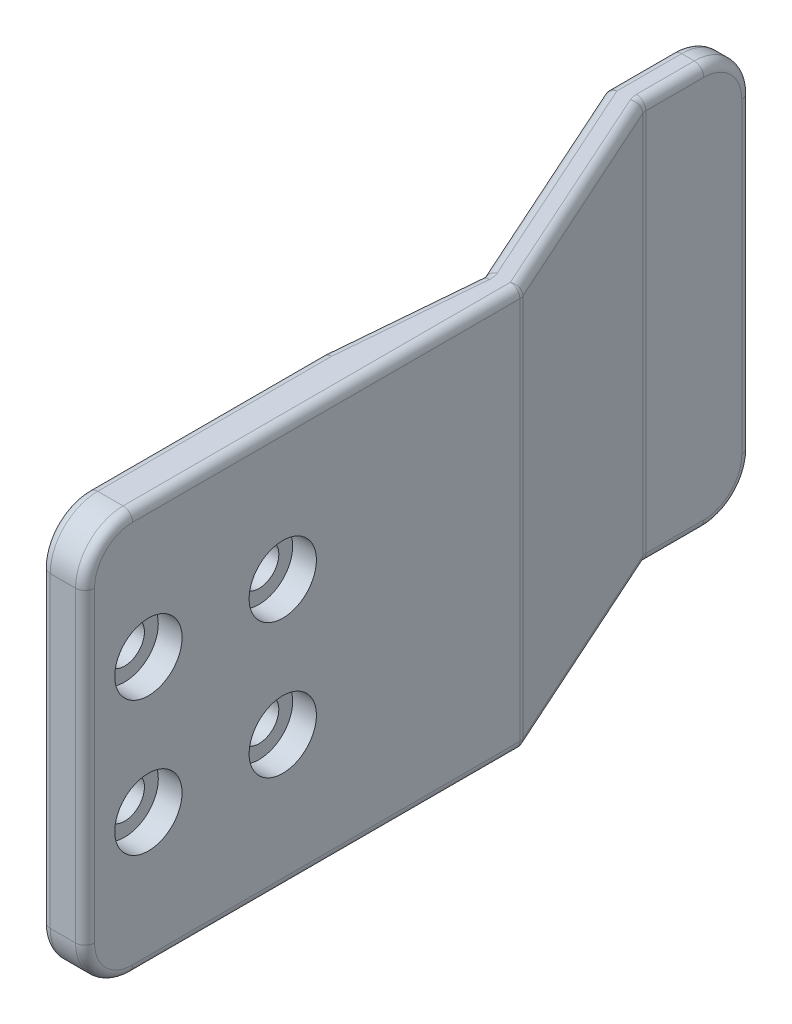
SolidWorks part; units mm, degrees
ref_plane "Front Plane" through (0, 0, 0) normal (0, 0, 1) x (1, 0, 0)
ref_plane "Top Plane" through (0, 0, 0) normal (0, 1, 0) x (1, 0, 0)
ref_plane "Right Plane" through (0, 0, 0) normal (1, 0, 0) x (0, 0, -1)
sketch "Sketch1" plane through (0, 0, 0) normal (0, 0, 1) x (1, 0, 0)
  line L0 (0, 0) -> (0, 24.7759) construction
  line L1 (0, 0) -> (34.3441, 0) construction
  line L3 (7, 12.7) -> (9, 12.7)
  line L4 (7, 12.7) -> (7, -12.7)
  line L5 (7, -12.7) -> (9, -12.7)
  line L6 (9, 12.7) -> (9, -12.7)
  line L7 (7, 12.7) -> (9, -12.7) construction
  line L8 (7, -12.7) -> (9, 12.7) construction
  point P3 (8, 0)
  dimension "D1" = 7
  dimension "D2" = 2
  dimension "D3" = 25.4
sketch "Sketch2" plane through (0, 0, 0) normal (0, 1, 0) x (1, 0, 0)
  line L0 (8, 0) -> (8, 27.37)
  line L1 (8, 27.37) -> (1.7, 41.37)
  line L2 (1.7, 41.37) -> (1.7, 48.37)
  line L3 (0, 0) -> (0, 51.9607) construction
  dimension "D1" = 1.7
  dimension "D2" = 7
  dimension "D4" = 21
  dimension "D3" = 48.37
sweep "Sweep1" add profiles "Sketch1" path "Sketch2"
sketch "Sketch8" plane through (9, 0, 0) normal (1, 0, 0) x (0, 0, -1)
  line L1 (12.4853, -4.2426) -> (4, -4.2426) construction
  line L2 (12.4853, -4.2426) -> (12.4853, 4.2426) construction
  line L3 (12.4853, 4.2426) -> (4, 4.2426) construction
  line L4 (4, -4.2426) -> (4, 4.2426) construction
  line L5 (12.4853, -4.2426) -> (4, 4.2426) construction
  line L6 (12.4853, 4.2426) -> (4, -4.2426) construction
  line L7 (0, -12.7) -> (0, 12.7) construction
  circle A0 centre (4, 4.2426) radius 1.25
  circle A1 centre (12.4853, 4.2426) radius 1.25
  circle A2 centre (4, -4.2426) radius 1.25
  circle A3 centre (12.4853, -4.2426) radius 1.25
  point P0 (8.2426, 0)
  dimension "D3" = 2.5
  dimension "D2" = 6
  dimension "D1" = 4
extrude "Bracket Thru Holes" cut sketch "Sketch8" against normal through all
sketch "Sketch9" plane through (7, 0, 0) normal (-1, 0, 0) x (0, 0, 1)
  line L0 (-12.4853, 4.2426) -> (-4, 4.2426) construction
  line L1 (-8.2426, 4.2426) -> (-8.2426, 12.7) construction
  line L2 (-27.1554, 12.7) -> (0, 12.7) construction
  line L3 (-27.1554, -12.7) -> (0, -12.7) construction
  line L4 (0, 12.7) -> (-16.4853, 12.7)
  line L5 (0, 12.7) -> (0, -12.7)
  line L6 (0, -12.7) -> (-16.4853, -12.7)
  line L7 (-16.4853, 12.7) -> (-16.4853, -12.7)
  circle A0 centre (-4, -4.2426) radius 1.25 construction
  circle A1 centre (-12.4853, -4.2426) radius 1.25 construction
  circle A2 centre (-4, 4.2426) radius 1.25 construction
  circle A3 centre (-12.4853, 4.2426) radius 1.25 construction
  circle A4 centre (-4, -4.2426) radius 1.25
  circle A5 centre (-12.4853, -4.2426) radius 1.25
  circle A6 centre (-4, 4.2426) radius 1.25
  circle A7 centre (-12.4853, 4.2426) radius 1.25
  point P15 (-8.2426, 12.7)
extrude "Bracket Thicken" add sketch "Sketch9" along normal blind 0.8
sketch "Sketch10" plane through (0, 12.7, 0) normal (0, 1, 0) x (1, 0, 0)
  line L0 (6.2, 16.4853) -> (6.2, 17.7853)
  line L1 (7, 27.1554) -> (7, 16.4853)
  line L2 (7, 16.4853) -> (6.2, 16.4853)
  line L3 (6.2, 17.7853) -> (7, 27.1554)
  dimension "D1" = 1.3
extrude "Bracket Thicken Chamfer" add sketch "Sketch10" against normal through all
sketch "Sketch11" plane through (9, 0, 0) normal (1, 0, 0) x (0, 0, -1)
  circle A0 centre (4, 4.2426) radius 2.125
  circle A1 centre (12.4853, 4.2426) radius 2.125
  circle A2 centre (4, -4.2426) radius 2.125
  circle A3 centre (12.4853, -4.2426) radius 2.125
  dimension "D1" = 4.25
extrude "Bracket Bore Holes" cut sketch "Sketch11" against normal blind 1.5
fillet "Fillet1" radius 3 4 edges at (7.6, 12.7, 0) (7.6, -12.7, 0) (1.7, -12.7, -48.37) (1.7, 12.7, -48.37)
fillet "Fillet2" radius 0.6 31 edges at (0.7, -11.8213, -47.4913) (0.7, 0, -48.37) (0.7, 11.8213, -47.4913) (2.7, -11.8213, -47.4913) (2.7, 0, -48.37) (2.7, 11.8213, -47.4913) (9, -11.8213, -0.8787) (9, 0, 0) (9, 11.8213, -0.8787) (6.2, -11.8213, -0.8787) (6.2, 0, 0) (6.2, 11.8213, -0.8787) (5.85, -12.7, -34.5846) (2.7, -12.7, -43.4773) (0.7, -12.7, -43.2627) (3.85, -12.7, -34.1554) (6.2, -12.7, -10.3926) (9, -12.7, -15.2923) (3.85, 12.7, -34.1554) (0.7, 12.7, -43.2627) (2.7, 12.7, -43.4773) (5.85, 12.7, -34.5846) (9, 12.7, -15.2923) (6.2, 12.7, -10.3926) (0.7, 0, -41.1554) (2.7, 0, -41.5846) (9, 0, -27.5846) (6.6, -12.7, -22.4703) (6.6, 12.7, -22.4703) (7, 0, -27.1554) (6.2, 0, -17.7853)
equation "\"D1@Sketch1\"=21.00mm/3"
equation "\"D3@Sketch1\"=76.20mm/3"
equation "\"D4@Sketch2\"=21"
equation "\"D3@Sketch2\"=48.57-0.2"
equation "\"PLA_shrink\"=0.3mm"
equation "\"fit_sliding\"=0.5mm"
equation "\"fit_snap\"=0.3mm"
equation "\"fit_tight\"=0.2mm"
equation "\"m2_tap\"= 1.75mm + \"PLA_shrink\""
equation "\"m2_standard\"= 2.2mm + \"PLA_shrink\""
equation "\"m2_head\"= 3.45mm + \"PLA_shrink\""
equation "\"m2.5_tap\"= 2.05 + \"PLA_shrink\""
equation "\"m2.5_standard\"= 2.75 + \"PLA_shrink\""
equation "\"m2.5_head\"= 5mm + \"PLA_shrink\""
equation "\"m3_tap\"= 2.5mm + \"PLA_shrink\""
equation "\"m3_standard\"= 3.3mm + \"PLA_shrink\""
equation "\"m3_head\"= 6mm + \"PLA_shrink\""
equation "\"connector_width\"= 9.35mm"
equation "\"wire_width\"= 3.1mm + \"PLA_shrink\""
equation "\"D3@Sketch8\"=\"m2_standard\""
equation "\"D1@Sketch11\"=\"m2_head\"+\"fit_sliding\""
equation "\"D1@Sketch2\"=2.00mm-0.3"
equation "\"m2_thin_wall\"= 1.9mm + \"PLA_shrink\""
